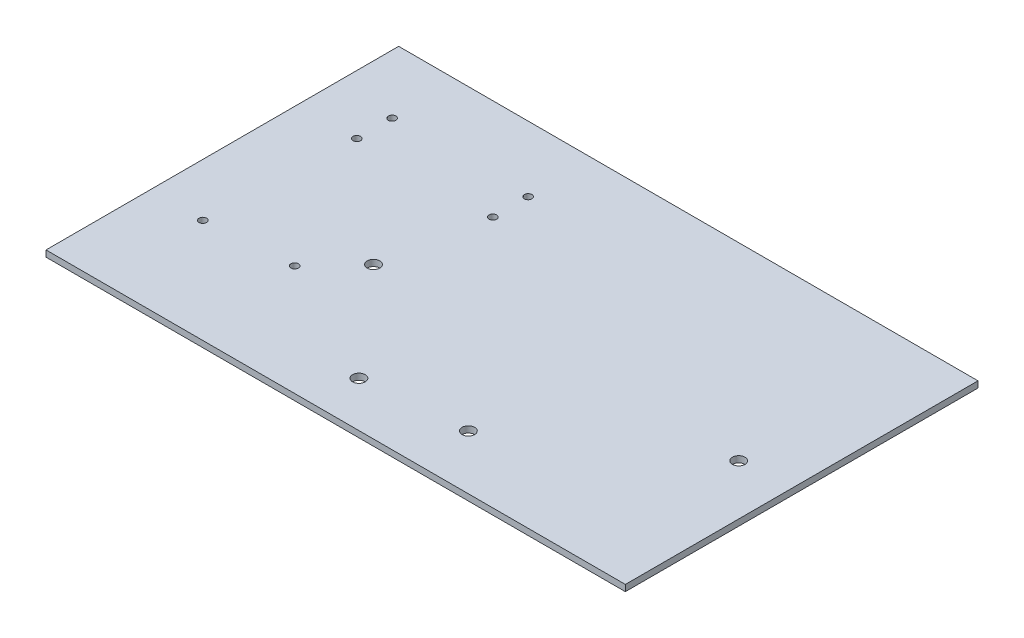
SolidWorks part; units mm, degrees
ref_plane "Front Plane" through (0, 0, 0) normal (0, 0, 1) x (1, 0, 0)
ref_plane "Top Plane" through (0, 0, 0) normal (0, 1, 0) x (1, 0, 0)
ref_plane "Right Plane" through (0, 0, 0) normal (1, 0, 0) x (0, 0, -1)
sketch "Sketch1" plane through (0, 0, 0) normal (0, 1, 0) x (1, 0, 0)
  line L1 (-158.75, 88.9) -> (158.75, 88.9)
  line L2 (-158.75, 88.9) -> (-158.75, -88.9)
  line L3 (-158.75, -88.9) -> (158.75, -88.9)
  line L4 (158.75, 88.9) -> (158.75, -88.9)
  line L5 (-158.75, 88.9) -> (158.75, -88.9) construction
  line L6 (-158.75, -88.9) -> (158.75, 88.9) construction
  circle A0 centre (-69.85, -12.7) radius 3.175
  circle A1 centre (107.95, -6.35) radius 3.175
  circle A4 centre (-129.032, 55.88) radius 1.905
  circle A5 centre (-60.452, 55.88) radius 1.905
  circle A7 centre (-129.032, 38.1) radius 1.905
  circle A8 centre (-60.452, 38.1) radius 1.905
  point P0 (0, 0)
  dimension "D3" = 6.35
  dimension "D4" = 6.35
  dimension "D14" = 3.81
  dimension "D17" = 17.78
  dimension "D1" = 317.5
  dimension "D2" = 177.8
  dimension "D5" = 88.9
  dimension "D6" = 266.7
  dimension "D7" = 95.25
  dimension "D8" = 76.2
  dimension "D13" = 29.718
  dimension "D15" = 68.58
  dimension "D16" = 127
extrude "Boss-Extrude1" add sketch "Sketch1" along normal blind 3.175
sketch "Sketch2" plane through (0, 3.175, 0) normal (0, 1, 0) x (1, 0, 0)
  line L0 (-158.75, 88.9) -> (-158.75, -88.9) construction
  line L1 (-158.75, -88.9) -> (158.75, -88.9) construction
  circle A0 centre (-89.0817, -33.177) radius 1.905
  circle A1 centre (-132.1376, -36.4483) radius 1.905
  dimension "D1" = 3.81
  dimension "D2" = 69.6683
  dimension "D3" = 52.4517
  dimension "D4" = 55.723
  dimension "D5" = 43.18
extrude "Cut-Extrude1" cut sketch "Sketch2" against normal through all
sketch "Sketch3" plane through (0, 0, 0) normal (0, -1, 0) x (-1, 0, 0)
  line L0 (158.75, -88.9) -> (-158.75, -88.9) construction
  line L1 (158.75, 88.9) -> (158.75, -88.9) construction
  circle A0 centre (23.8295, -66.04) radius 3.175
  circle A1 centre (-26.7643, -61.468) radius 3.175
  dimension "D1" = 6.35
  dimension "D2" = 4.572
  dimension "D3" = 22.86
  dimension "D4" = 185.5143
  dimension "D5" = 50.8
extrude "Cut-Extrude2" cut sketch "Sketch3" against normal through all
sketch "Sketch4" plane through (0, 3.175, 0) normal (0, 1, 0) x (1, 0, 0)
  line L0 (-158.75, -88.9) -> (158.75, -88.9) construction
  line L1 (158.75, 88.9) -> (133.35, 88.9)
  line L2 (158.75, 88.9) -> (158.75, -88.9)
  line L3 (158.75, -88.9) -> (133.35, -88.9)
  line L4 (133.35, 88.9) -> (133.35, -88.9)
  dimension "D1" = 25.4
extrude "Cut-Extrude3" cut sketch "Sketch4" against normal through all
